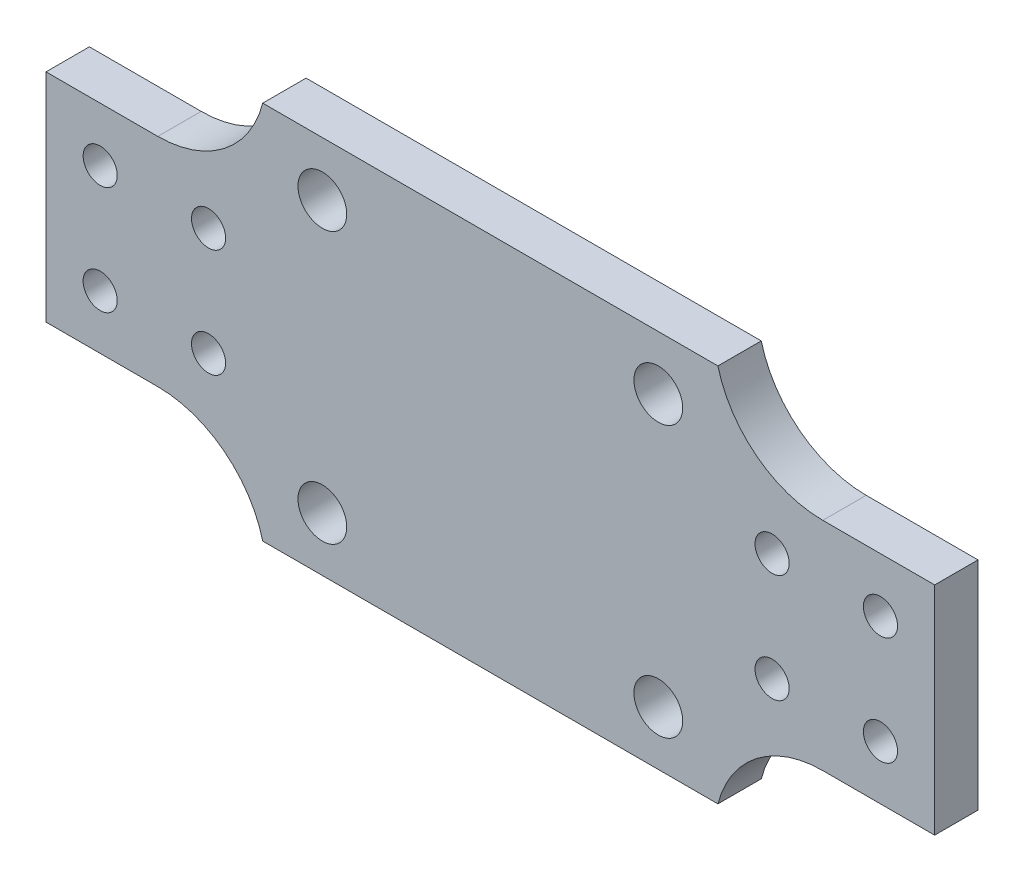
SolidWorks part; units mm, degrees
ref_plane "前视基准面" through (0, 0, 0) normal (0, 0, 1) x (1, 0, 0)
ref_plane "上视基准面" through (0, 0, 0) normal (0, 1, 0) x (1, 0, 0)
ref_plane "右视基准面" through (0, 0, 0) normal (1, 0, 0) x (0, 0, -1)
other "Configuration Table"
sketch "草图1" plane through (0, 0, 0) normal (0, 0, 1) x (1, 0, 0)
  line L1 (0, 0) -> (82, 0)
  line L2 (0, 0) -> (0, -20)
  line L3 (0, -20) -> (82, -20)
  line L4 (82, 0) -> (82, -20)
  dimension "D1" = 20
  dimension "D2" = 82
extrude "凸台-拉伸1" add sketch "草图1" along normal blind 4
sketch "草图2" plane through (0, 0, 4) normal (0, 0, 1) x (1, 0, 0)
  line L0 (41, 0) -> (41, -10) construction
  line L1 (62, -27.5) -> (20, -27.5)
  line L2 (62, -27.5) -> (62, 7.5)
  line L3 (62, 7.5) -> (20, 7.5)
  line L4 (20, -27.5) -> (20, 7.5)
  line L5 (62, -27.5) -> (20, 7.5) construction
  line L6 (62, 7.5) -> (20, -27.5) construction
  line L7 (82, 0) -> (0, 0) construction
  line L8 (41, -10) -> (0, -10) construction
  line L9 (0, 0) -> (0, -20) construction
  point P0 (41, -10)
  dimension "D1" = 42
  dimension "D2" = 35
extrude "凸台-拉伸2" add sketch "草图2" against normal up to surface (4 mm away) up to face at (41, -10, 0)
sketch "草图3" plane through (0, 0, 4) normal (0, 0, 1) x (1, 0, 0)
  line L0 (41, 7.5) -> (41, -27.5) construction
  line L1 (62, 7.5) -> (20, 7.5) construction
  line L2 (20, -27.5) -> (62, -27.5) construction
  line L3 (0, -10) -> (10, -10) construction
  line L4 (0, 0) -> (0, -20) construction
  line L5 (10, -10) -> (10, 0) construction
  line L6 (20, 0) -> (0, 0) construction
  line L7 (72, -10) -> (72, 0) construction
  line L8 (82, -10) -> (72, -10) construction
  circle A0 centre (5, -5) radius 1.575
  circle A1 centre (15, -5) radius 1.575
  circle A2 centre (15, -15) radius 1.575
  circle A3 centre (5, -15) radius 1.575
  circle A4 centre (77, -15) radius 1.575
  circle A5 centre (67, -15) radius 1.575
  circle A6 centre (67, -5) radius 1.575
  circle A7 centre (77, -5) radius 1.575
  circle A8 centre (25.5, 2.5) radius 2.25
  circle A9 centre (56.5, 2.5) radius 2.25
  circle A10 centre (56.5, -22.5) radius 2.25
  circle A11 centre (25.5, -22.5) radius 2.25
  dimension "D1" = 3.15
  dimension "D4" = 4.5
  dimension "D2" = 5
  dimension "D3" = 5
  dimension "D5" = 15.5
  dimension "D6" = 12.5
extrude "切除-拉伸1" cut sketch "草图3" against normal through all
fillet "圆角1" radius 10 4 edges at (62, -20, 2) (20, -20, 2) (20, 0, 2) (62, 0, 2)
